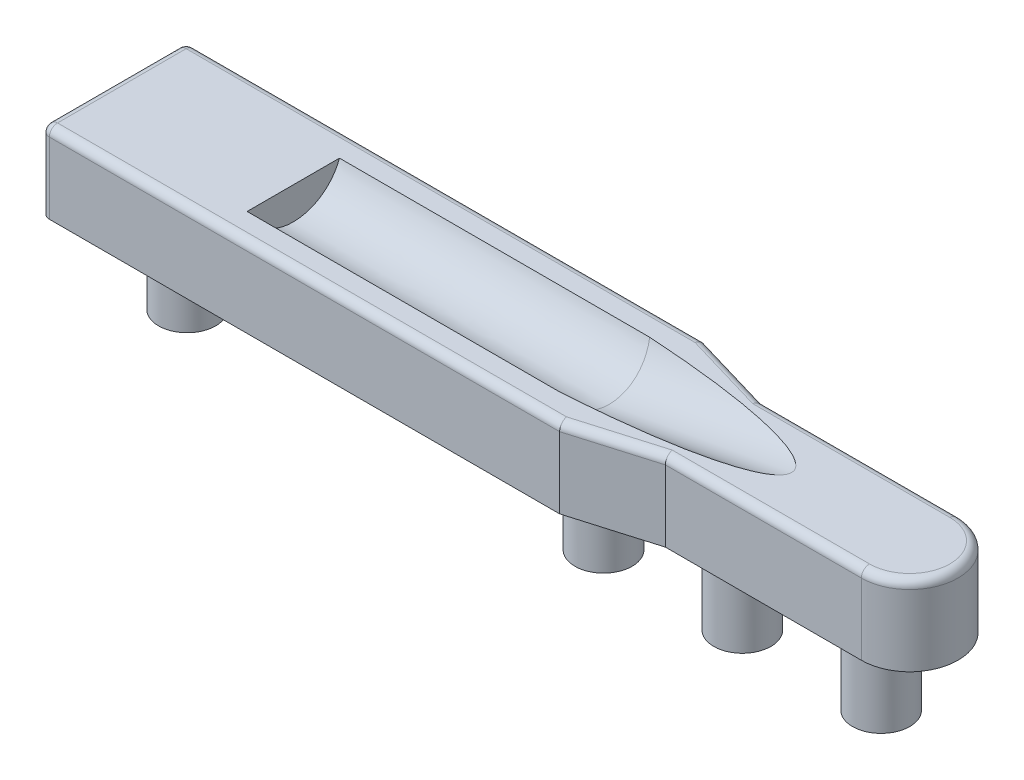
SolidWorks part; units mm, degrees
ref_plane "Front Plane" through (0, 0, 0) normal (0, 0, 1) x (1, 0, 0)
ref_plane "Top Plane" through (0, 0, 0) normal (0, 1, 0) x (1, 0, 0)
ref_plane "Right Plane" through (0, 0, 0) normal (1, 0, 0) x (0, 0, -1)
sketch "Sketch1" plane through (0, 0, 0) normal (0, 0, 1) x (1, 0, 0)
  line L1 (-17.469, 9.1211) -> (86.531, 9.1211)
  line L2 (-17.469, 9.1211) -> (-17.469, -0.5989)
  line L3 (-17.469, -0.5989) -> (86.531, -0.5989)
  line L4 (86.531, 9.1211) -> (86.531, -0.5989)
  dimension "D1" = 9.72
  dimension "D2" = 104
extrude "body" add sketch "Sketch1" along normal blind 17.75
sketch "Sketch2" plane through (0, -0.5989, 0) normal (0, -1, 0) x (1, 0, 0)
  line L7 (80.031, 17.75) -> (80.031, 0) construction
  line L8 (46.031, 17.75) -> (56.031, 14.8)
  line L9 (56.031, 14.8) -> (80.031, 14.8)
  line L10 (80.031, 2.95) -> (56.031, 2.95)
  line L11 (46.031, 0) -> (56.031, 2.95)
  line L12 (46.031, 17.75) -> (86.531, 17.75)
  line L13 (86.531, 17.75) -> (86.531, 0)
  line L14 (86.531, 0) -> (46.031, 0)
  line L15 (-17.469, 17.75) -> (86.531, 17.75) construction
  line L16 (86.531, 17.75) -> (86.531, 0) construction
  line L17 (-17.469, 17.75) -> (-17.469, 0) construction
  line L18 (-17.469, 0) -> (86.531, 0) construction
  arc A1 (80.031, 2.95) -> (80.031, 14.8) centre (80.031, 8.875) ccw
  dimension "D2" = 24
  dimension "D3" = 24
  dimension "D4" = 6.5
  dimension "D5" = 63.5
  dimension "D6" = 11.85
  dimension "D7" = 0
  dimension "D8" = 0
  dimension "D9" = 63.5
  dimension "D10" = 0
extrude "front_cut_out" cut sketch "Sketch2" against normal through all
sketch "Sketch4" plane through (0, -0.5989, 0) normal (0, -1, 0) x (1, 0, 0)
  line L0 (-17.469, 0) -> (46.031, 0) construction
  line L1 (-17.469, 17.75) -> (-17.469, 0) construction
  line L2 (-8.469, 17.75) -> (-8.469, 0) construction
  line L3 (-17.469, 17.75) -> (46.031, 17.75) construction
  line L4 (59.531, 14.8) -> (59.531, 2.95) construction
  line L5 (56.031, 14.8) -> (80.031, 14.8) construction
  line L6 (80.031, 2.95) -> (56.031, 2.95) construction
  line L7 (76.531, 14.8) -> (76.531, 2.95) construction
  circle A0 centre (-8.469, 8.875) radius 3.5
  circle A1 centre (42.531, 8.875) radius 3.5
  circle A2 centre (59.531, 8.875) radius 3.5
  circle A3 centre (76.531, 8.875) radius 3.5
  dimension "D1" = 7
  dimension "D3" = 7
  dimension "D4" = 7
  dimension "D2" = 51
  dimension "D6" = 9
  dimension "D7" = 68
  dimension "D8" = 85
extrude "interface_deep" add sketch "Sketch4" along normal blind 10
sketch "bullet_cut_out_reference" plane through (0, 9.1211, 0) normal (0, 1, 0) x (1, 0, 0)
  line L0 (42.531, 7.4897) -> (42.531, -24.3565) construction
  line L1 (-17.469, -17.75) -> (-17.469, 0) construction
  dimension "D1" = 60
ref_plane "Plane1" through (42.8083, 7.5483, 0) normal (0.9848, 0.1736, 0) x (0, 0, 1)
sketch "Sketch7" plane through (42.8083, 7.5483, 0) normal (0.9848, 0.1736, 0) x (0, 0, 1)
  line L0 (-7.4897, -1.5971) -> (24.3565, -1.5971) construction
  line L1 (17.75, -3.5971) -> (0, -3.5971) construction
  line L3 (17.75, -0.9893) -> (17.75, -12.016) construction
  line L4 (0, -0.9893) -> (0, -12.016) construction
  circle A0 centre (8.875, -3.5971) radius 6
  dimension "D1" = 12
  dimension "D2" = 2
extrude "bullet_platform" cut sketch "Sketch7" along normal through all
ref_plane "Plane2" through (4.531, 0, 0) normal (-1, 0, 0) x (0, 0, 1)
sketch "Sketch8" plane through (4.531, 0, 0) normal (-1, 0, 0) x (0, 0, 1)
  line L0 (3.2181, 9.1211) -> (3.2181, 12.3176)
  line L1 (3.2181, 12.3176) -> (14.5319, 12.3176)
  line L2 (14.5319, 12.3176) -> (14.5319, 9.1211)
  ellipse E2 centre (8.875, 11.0907) end of major axis (14.875, 11.0907) minor radius 5.9088 (3.2181, 9.1211) -> (14.5319, 9.1211) ccw
  ellipse E3 centre (8.875, 11.0907) end of major axis (14.875, 11.0907) minor radius 5.9088 (3.2181, 9.1211) -> (14.5319, 9.1211) ccw
  dimension "D1" = 0
extrude "bullet_platform_extended" cut sketch "Sketch8" against normal up to next
fillet "Fillet1" radius 1 8 edges at (14.281, 9.1211, 17.75) (51.031, 9.1211, 16.275) (68.031, 9.1211, 14.8) (85.956, 9.1211, 8.875) (68.031, 9.1211, 2.95) (51.031, 9.1211, 1.475) (14.281, 9.1211, 0) (-17.469, 9.1211, 8.875)
fillet "Fillet2" radius 1 4 edges at (-17.1761, 8.8282, 0.2929) (-17.1761, 8.8282, 17.4571) (-17.469, 3.7611, 0) (-17.469, 3.7611, 17.75)
